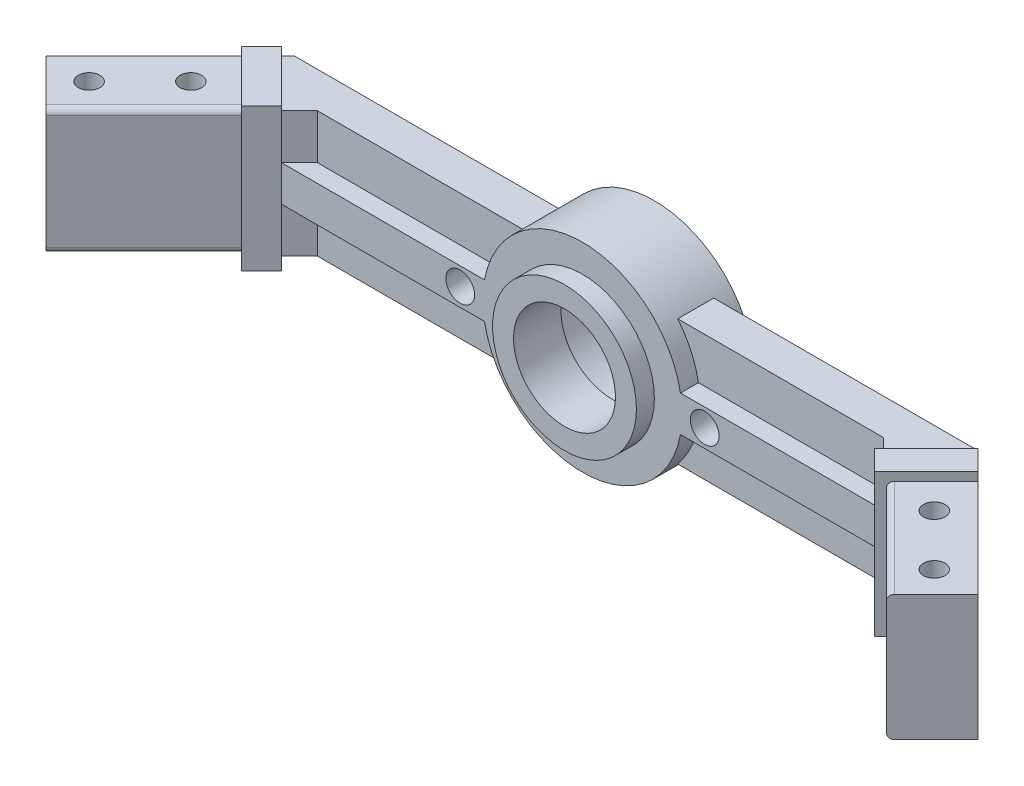
SolidWorks part; units mm, degrees
ref_plane "Front Plane" through (0, 0, 0) normal (0, 0, 1) x (1, 0, 0)
ref_plane "Top Plane" through (0, 0, 0) normal (0, 1, 0) x (1, 0, 0)
ref_plane "Right Plane" through (0, 0, 0) normal (1, 0, 0) x (0, 0, -1)
sketch "Sketch2" plane through (0, 0, 0) normal (0, 1, 0) x (1, 0, 0)
  line L0 (-57.15, 0) -> (57.15, 0)
  line L1 (57.15, 0) -> (84.0908, -26.9408)
  line L2 (0, 0) -> (0, 42.1572) construction
  line L3 (84.0908, -26.9408) -> (76.0085, -35.023)
  line L4 (76.0085, -35.023) -> (53.6855, -12.7)
  line L5 (53.6855, -12.7) -> (-53.6855, -12.7)
  line L6 (0, -12.7) -> (0, 0)
  line L7 (-76.0085, -35.023) -> (-53.6855, -12.7)
  line L8 (-84.0908, -26.9408) -> (-76.0085, -35.023)
  line L9 (-57.15, 0) -> (-84.0908, -26.9408)
  dimension "D1" = 135
  dimension "D2" = 57.15
  dimension "D3" = 38.1
  dimension "D4" = 12.7
  dimension "D5" = 11.43
extrude "Boss-Extrude1" add sketch "Sketch2" along normal mid plane 22.225 contours L0 L9 L8 L7 L5 L6 | L6 L5 L4 L3 L1 L0 region at (-42.209, 0, 10.6991) region at (42.209, 0, 10.6991)
sketch "Sketch3" plane through (0, 0, 0) normal (0, 0, -1) x (-1, 0, 0)
  circle A0 centre (0, 0) radius 11.25
  circle A1 centre (0, 0) radius 17.6
  circle A2 centre (0, 0) radius 9
  line M2 (-57.15, -11.1125) -> (57.15, -11.1125)
  line M4 (57.15, 11.1125) -> (-57.15, 11.1125)
  dimension "D1" = 22.5
  dimension "D2" = 6.35
  dimension "D3" = 18
extrude "Boss-Extrude2" add sketch "Sketch3" against normal up to surface (12.7 mm away) contours A1 up to face at (0, 0, 12.7)
extrude "Cut-Extrude2" cut sketch "Sketch3<5>" against normal blind 7.5 contours A0 M4 M2 | A2 | A0 M4 | A0 region at (-8.312, -7.1033, 0) region at (0, 11.1675, 0) region at (0, 0, 0)
sketch "Sketch3<5>" plane through (0, 0, 0) normal (0, 0, -1) x (-1, 0, 0) same geometry as "Sketch3"
extrude "Cut-Extrude3" cut sketch "Sketch3<6>" against normal up to surface (12.7 mm away) contours A2 up to face at (0, 0, 12.7)
sketch "Sketch3<6>" plane through (0, 0, 0) normal (0, 0, -1) x (-1, 0, 0) same geometry as "Sketch3"
sketch "Sketch4" plane through (55.5158, 0, 55.5158) normal (0.7071, 0, 0.7071) x (0.7071, 0, -0.7071)
  line L0 (34.6962, 11.1125) -> (34.6962, -11.1125) construction
  line L2 (40.4112, -12.6125) -> (27.4812, -12.6125)
  line L3 (40.4112, -12.6125) -> (40.4112, 12.6125)
  line L4 (28.9812, -11.1125) -> (40.4112, -11.1125)
  line L5 (40.4112, -11.1125) -> (40.4112, 11.1125)
  line L6 (40.4112, 11.1125) -> (28.9812, 11.1125)
  line L7 (28.9812, 11.1125) -> (28.9812, -11.1125)
  line L8 (28.9812, -11.1125) -> (40.4112, -11.1125)
  line L9 (40.4112, -11.1125) -> (40.4112, 11.1125)
  line L10 (40.4112, 11.1125) -> (28.9812, 11.1125)
  line L11 (28.9812, 11.1125) -> (28.9812, -11.1125)
  line L12 (40.4112, 12.6125) -> (27.4812, 12.6125)
  line L13 (27.4812, -12.6125) -> (27.4812, 12.6125)
  line M9 (28.9812, -11.1125) -> (40.4112, -11.1125)
  line M11 (40.4112, 11.1125) -> (28.9812, 11.1125)
  line M12 (28.9812, 11.1125) -> (28.9812, -11.1125)
  dimension "D2" = 1.5
  dimension "D3" = 1.5
  dimension "D4" = 1.5
  dimension "D1" = 0
extrude "Boss-Extrude3" add sketch "Sketch4" against normal blind 3.175 and the other way blind 1.778 from offset 28.7528 contours L13 L2 L3 L8 L10 L12 M9 M12 M11 region at (79.5193, -12.329, 31.5122) offset against normal yes
fillet "Fillet1" radius 1.016 2 edges at (66.4715, -11.1125, 25.486) (66.4715, 11.1125, 25.486)
sketch "Sketch5" plane through (0, 11.1125, 0) normal (0, 1, 0) x (1, 0, 0)
  line L0 (80.2293, -30.8023) -> (61.1552, -11.7282) construction
  line L4 (65.0167, -7.8667) -> (57.6529, -15.2305)
  line L5 (57.6529, -15.2305) -> (76.727, -34.3046)
  line L6 (76.727, -34.3046) -> (84.0908, -26.9408)
  line L7 (84.0908, -26.9408) -> (65.0167, -7.8667)
  line L8 (65.0167, -7.8667) -> (57.6529, -15.2305)
  line L9 (57.6529, -15.2305) -> (76.727, -34.3046)
  line L10 (76.727, -34.3046) -> (84.0908, -26.9408)
  line L11 (84.0908, -26.9408) -> (65.0167, -7.8667)
  circle A0 centre (74.6256, -25.1986) radius 1.905
  circle A1 centre (65.6453, -16.2183) radius 1.905
  dimension "D4" = 3.81
  dimension "D2" = 6.35
  dimension "D3" = 12.7
  dimension "D5" = 5.461
  dimension "D1" = 0
extrude "Cut-Extrude4" cut sketch "Sketch5" against normal through all contours A0 L0 | L0 A0 | A1 region at (74.0539, 11.1125, 25.7703) region at (75.1973, 11.1125, 24.6269)
mirror "Mirror2" about plane through (0, 0, 0) normal (1, 0, 0) of "Boss-Extrude3", "Cut-Extrude4"
fillet "Fillet3" radius 1.016 2 edges at (-66.4715, -11.1125, 25.486) (-66.4715, 11.1125, 25.486)
sketch "Sketch6" plane through (0, 0, 12.7) normal (0, 0, 1) x (1, 0, 0)
  line L0 (-53.1788, 0) -> (53.1788, 0) construction
  line L1 (-53.1788, 3.175) -> (-17.3112, 3.175)
  line L2 (-53.1788, -3.175) -> (-17.3112, -3.175)
  line L3 (0, 0) -> (0, 17.6) construction
  line L4 (53.1788, -3.175) -> (17.3112, -3.175)
  line L5 (53.1788, 3.175) -> (17.3112, 3.175)
  line L6 (13.6482, -11.1125) -> (53.1788, -11.1125)
  line L7 (53.1788, -11.1125) -> (53.1788, 11.1125)
  line L8 (53.1788, 11.1125) -> (13.6482, 11.1125)
  line L9 (-13.6482, 11.1125) -> (-53.1788, 11.1125)
  line L11 (-53.1788, -11.1125) -> (-13.6482, -11.1125)
  line L12 (13.6482, -11.1125) -> (53.1788, -11.1125)
  line L14 (53.1788, 11.1125) -> (13.6482, 11.1125)
  line L15 (-13.6482, 11.1125) -> (-53.1788, 11.1125)
  line L17 (-53.1788, -11.1125) -> (-13.6482, -11.1125)
  line L29 (53.1788, -11.1125) -> (53.1788, 11.1125)
  line L31 (-53.1788, 11.1125) -> (-53.1788, -11.1125)
  line L34 (-53.1788, 11.1125) -> (-53.1788, -11.1125)
  circle A0 centre (0, 0) radius 9 construction
  circle A1 centre (0, 0) radius 9
  arc A2 (13.6482, 11.1125) -> (-13.6482, 11.1125) centre (0, 0) ccw
  arc A3 (-13.6482, -11.1125) -> (13.6482, -11.1125) centre (0, 0) ccw
  arc A4 (13.6482, 11.1125) -> (-13.6482, 11.1125) centre (0, 0) ccw
  arc A5 (-13.6482, -11.1125) -> (13.6482, -11.1125) centre (0, 0) ccw
  circle A6 centre (0, 0) radius 17.6
  line M16 (13.6482, -11.1125) -> (53.1788, -11.1125)
  line M17 (53.1788, -11.1125) -> (53.1788, 11.1125)
  line M18 (53.1788, 11.1125) -> (13.6482, 11.1125)
  line M20 (-13.6482, 11.1125) -> (-53.1788, 11.1125)
  line M22 (-53.1788, -11.1125) -> (-13.6482, -11.1125)
  dimension "D2" = 3.175
  dimension "D1" = 0
extrude "Cut-Extrude5" cut sketch "Sketch6" against normal blind 3.175 contours A6 L1 M20 | A6 L2 M22 | A6 L4 M16 M17 | A6 L5 M17 M18 region at (-34.5174, 7.2077, 12.7) region at (-34.5174, -7.2077, 12.7) region at (34.5174, 7.2077, 12.7) region at (34.5174, -7.2077, 12.7)
sketch "Sketch9" plane through (0, 0, 0) normal (0, 0, -1) x (-1, 0, 0)
  line L0 (0, 0) -> (-57.15, 0) construction
  line L1 (-57.15, 11.1125) -> (-57.15, -11.1125) construction
  line L2 (-17.3112, -3.175) -> (-68.1112, -3.175)
  line L3 (-68.1112, -3.175) -> (-68.1112, 3.175)
  line L4 (-17.3112, 3.175) -> (-68.1112, 3.175)
  line L5 (0, 19.2626) -> (0, -19.2626) construction
  line L6 (68.1112, -3.175) -> (68.1112, 3.175)
  line L7 (17.3112, 3.175) -> (68.1112, 3.175)
  line L8 (17.3112, -3.175) -> (68.1112, -3.175)
  line L10 (-57.15, -11.1125) -> (-68.1112, -11.1125)
  line L11 (-57.15, -11.1125) -> (-57.15, -3.175)
  line L12 (-57.15, -3.175) -> (-68.1112, -3.175)
  line L13 (-68.1112, -11.1125) -> (-68.1112, -3.175)
  line L14 (-68.1112, 3.175) -> (-57.15, 3.175)
  line L15 (57.15, 11.1125) -> (13.6482, 11.1125)
  line L16 (-13.6482, 11.1125) -> (-57.15, 11.1125)
  line L17 (-57.15, 11.1125) -> (-57.15, -11.1125)
  line L18 (-57.15, -11.1125) -> (-13.6482, -11.1125)
  line L19 (13.6482, -11.1125) -> (57.15, -11.1125)
  line L20 (57.15, -11.1125) -> (57.15, 11.1125)
  line L21 (57.15, 11.1125) -> (13.6482, 11.1125)
  line L22 (-13.6482, 11.1125) -> (-57.15, 11.1125)
  line L23 (-57.15, 11.1125) -> (-57.15, -11.1125)
  line L24 (-57.15, -11.1125) -> (-13.6482, -11.1125)
  line L25 (13.6482, -11.1125) -> (57.15, -11.1125)
  line L26 (57.15, -11.1125) -> (57.15, 11.1125)
  line L27 (-68.1112, 3.175) -> (-68.1112, 11.1125)
  line L28 (-68.1112, 11.1125) -> (-57.15, 11.1125)
  line L29 (-57.15, 3.175) -> (-57.15, 11.1125)
  line L30 (68.1112, -3.175) -> (57.15, -3.175)
  line L31 (68.1112, -3.175) -> (68.1112, -11.1125)
  line L32 (68.1112, -11.1125) -> (57.15, -11.1125)
  line L33 (57.15, -3.175) -> (57.15, -11.1125)
  line L34 (68.1112, 3.175) -> (57.15, 3.175)
  line L35 (68.1112, 3.175) -> (68.1112, 11.1125)
  line L36 (68.1112, 11.1125) -> (57.15, 11.1125)
  line L37 (57.15, 3.175) -> (57.15, 11.1125)
  circle A0 centre (0, 0) radius 17.6
  arc A3 (13.6482, 11.1125) -> (-13.6482, 11.1125) centre (0, 0) ccw
  arc A4 (-13.6482, -11.1125) -> (13.6482, -11.1125) centre (0, 0) ccw
  arc A5 (13.6482, 11.1125) -> (-13.6482, 11.1125) centre (0, 0) ccw
  arc A6 (-13.6482, -11.1125) -> (13.6482, -11.1125) centre (0, 0) ccw
  point P11 (-68.1112, 0)
  line M3 (57.15, 11.1125) -> (13.6482, 11.1125)
  line M5 (-13.6482, 11.1125) -> (-57.15, 11.1125)
  line M6 (-57.15, 11.1125) -> (-57.15, -11.1125)
  line M7 (-57.15, -11.1125) -> (-13.6482, -11.1125)
  line M9 (13.6482, -11.1125) -> (57.15, -11.1125)
  line M10 (57.15, -11.1125) -> (57.15, 11.1125)
  dimension "D1" = 3.175
  dimension "D2" = 50.8
  dimension "D3" = 0
extrude "Cut-Extrude6" cut sketch "Sketch9" against normal blind 3.175 contours L32 L31 L8 M10 | A0 L8 M9 M10 | A0 L7 M10 M3 | L35 L36 L7 M10 | A0 L2 M6 M7 | L13 L10 L2 M6 | A0 L4 M5 M6 | L28 L27 L4 M6 region at (36.5044, -7.2016, 0) region at (62.6306, -7.1438, 0) region at (36.5044, 7.2016, 0) region at (62.6306, 7.1437, 0) region at (-36.5044, -7.2016, 0) region at (-36.5044, 7.2016, 0) region at (-62.6306, -7.1438, 0) region at (-62.6306, 7.1437, 0)
sketch "Sketch12" plane through (55.5158, 0, 55.5158) normal (0.7071, 0, 0.7071) x (0.7071, 0, -0.7071)
  line L4 (28.9812, 10.0965) -> (28.9812, -10.0965)
  line L5 (29.9972, -11.1125) -> (40.4112, -11.1125)
  line L6 (40.4112, -11.1125) -> (40.4112, 11.1125)
  line L7 (40.4112, 11.1125) -> (29.9972, 11.1125)
  line L8 (28.9812, 10.0965) -> (28.9812, -10.0965)
  line L9 (29.9972, -11.1125) -> (40.4112, -11.1125)
  line L10 (40.4112, -11.1125) -> (40.4112, 11.1125)
  line L11 (40.4112, 11.1125) -> (29.9972, 11.1125)
  arc A2 (28.9812, -10.0965) -> (29.9972, -11.1125) centre (29.9972, -10.0965) ccw
  arc A3 (29.9972, 11.1125) -> (28.9812, 10.0965) centre (29.9972, 10.0965) ccw
  arc A4 (28.9812, -10.0965) -> (29.9972, -11.1125) centre (29.9972, -10.0965) ccw
  arc A5 (29.9972, 11.1125) -> (28.9812, 10.0965) centre (29.9972, 10.0965) ccw
  dimension "D1" = 0
extrude "Cut-Extrude9" cut sketch "Sketch12" against normal blind 2.54
mirror "Mirror3" about plane through (0, 0, 0) normal (1, 0, 0) of "Cut-Extrude9"
sketch "Sketch13" plane through (0, 0, 12.7) normal (0, 0, 1) x (1, 0, 0)
  circle A0 centre (0, 0) radius 9 construction
  circle A1 centre (0, 0) radius 9
  circle A2 centre (0, 0) radius 12.7
  dimension "D1" = 25.4
extrude "Boss-Extrude6" add sketch "Sketch13" along normal blind 3.175
chamfer "Chamfer2" distance 3.175 angle 45 4 edges at (53.1788, 7.1437, 9.525) (53.1788, -7.1437, 9.525) (-53.1788, 7.1437, 9.525) (-53.1788, -7.1437, 9.525)
sketch "Sketch14" plane through (0, 0, 0) normal (0, 0, -1) x (-1, 0, 0)
  line L6 (57.15, 3.175) -> (17.3112, 3.175)
  line L7 (-17.3112, 3.175) -> (-57.15, 3.175)
  line L8 (-57.15, 3.175) -> (-57.15, -3.175)
  line L9 (-57.15, -3.175) -> (-17.3112, -3.175)
  line L10 (17.3112, -3.175) -> (57.15, -3.175)
  line L11 (57.15, -3.175) -> (57.15, 3.175)
  line L12 (57.15, 3.175) -> (17.3112, 3.175)
  line L13 (-17.3112, 3.175) -> (-57.15, 3.175)
  line L14 (-57.15, 3.175) -> (-57.15, -3.175)
  line L15 (-57.15, -3.175) -> (-17.3112, -3.175)
  line L16 (17.3112, -3.175) -> (57.15, -3.175)
  line L17 (57.15, -3.175) -> (57.15, 3.175)
  circle A0 centre (0, 0) radius 11.25 construction
  circle A1 centre (0, 0) radius 11.25
  arc A2 (17.3112, 3.175) -> (-17.3112, 3.175) centre (0, 0) ccw
  arc A3 (-17.3112, -3.175) -> (17.3112, -3.175) centre (0, 0) ccw
  arc A4 (17.3112, 3.175) -> (-17.3112, 3.175) centre (0, 0) ccw
  arc A5 (-17.3112, -3.175) -> (17.3112, -3.175) centre (0, 0) ccw
  dimension "D1" = 0
sketch "Sketch15" plane through (0, 0, 0) normal (0, 0, -1) x (-1, 0, 0)
  line L0 (0, 0) -> (0, -17.6) construction
  arc A0 (-17.3112, -3.175) -> (17.3112, -3.175) centre (0, 0) ccw construction
  circle A1 centre (21.59, 0) radius 2.54
  circle A2 centre (-21.59, 0) radius 2.54
  dimension "D1" = 5.08
  dimension "D2" = 21.59
extrude "Cut-Extrude10" cut sketch "Sketch15" against normal through all contours A1 | A2
sketch "Sketch16" plane through (0, -11.1125, 0) normal (0, -1, 0) x (1, 0, 0)
  line L0 (74.9309, 32.5085) -> (74.2125, 33.2269) construction
  line L1 (74.2125, 33.2269) -> (56.9345, 15.9489) construction
  line L2 (57.6529, 15.2305) -> (56.9345, 15.9489) construction
  line L3 (-56.9345, 15.9489) -> (-74.2125, 33.2269) construction
  line L4 (-74.2125, 33.2269) -> (-74.9309, 32.5085) construction
  line L5 (-56.9345, 15.9489) -> (-57.6529, 15.2305) construction
  line L6 (-65.0167, 7.8667) -> (-61.5144, 4.3644) construction
  line L7 (-61.5144, 4.3644) -> (-52.3715, 13.5073) construction
  line L8 (-52.3715, 13.5073) -> (-55.8738, 17.0096) construction
  line L9 (-55.8738, 17.0096) -> (-65.0167, 7.8667) construction
  line L10 (55.8738, 17.0096) -> (52.3715, 13.5073) construction
  line L11 (52.3715, 13.5073) -> (61.5144, 4.3644) construction
  line L12 (61.5144, 4.3644) -> (65.0167, 7.8667) construction
  line L13 (65.0167, 7.8667) -> (55.8738, 17.0096) construction
  line L14 (17.3112, 9.525) -> (13.6482, 9.525) construction
  line L15 (17.3112, 12.7) -> (-17.3112, 12.7) construction
  line L16 (-13.6482, 9.525) -> (-17.3112, 9.525) construction
  line L17 (-17.3112, 3.175) -> (-13.6482, 3.175) construction
  line L18 (-17.3112, 0) -> (17.3112, 0) construction
  line L19 (13.6482, 3.175) -> (17.3112, 3.175) construction
  line L20 (-17.3112, 12.7) -> (-53.1788, 12.7) construction
  line L21 (-53.1788, 12.7) -> (-50.0038, 9.525) construction
  line L22 (-50.0038, 9.525) -> (-17.3112, 9.525) construction
  line L23 (-60.325, 3.175) -> (-57.15, 0) construction
  line L24 (-57.15, 0) -> (-17.3112, 0) construction
  line L25 (-17.3112, 3.175) -> (-60.325, 3.175) construction
  line L26 (17.3112, 9.525) -> (50.0038, 9.525) construction
  line L27 (50.0038, 9.525) -> (53.1788, 12.7) construction
  line L28 (53.1788, 12.7) -> (17.3112, 12.7) construction
  line L29 (57.15, 0) -> (60.325, 3.175) construction
  line L30 (60.325, 3.175) -> (17.3112, 3.175) construction
  line L31 (17.3112, 0) -> (57.15, 0) construction
  line L32 (-74.9309, 32.5085) -> (-82.2947, 25.1447) construction
  line L33 (-82.2947, 25.1447) -> (-65.0167, 7.8667) construction
  line L34 (-65.0167, 7.8667) -> (-57.6529, 15.2305) construction
  line L35 (-60.325, 3.175) -> (-13.6482, 3.175) construction
  line L36 (-13.6482, 9.525) -> (-50.0038, 9.525) construction
  line L37 (-50.0038, 9.525) -> (-53.1788, 12.7) construction
  line L38 (-53.1788, 12.7) -> (-61.5144, 4.3644) construction
  line L39 (-61.5144, 4.3644) -> (-60.325, 3.175) construction
  line L40 (13.6482, 3.175) -> (60.325, 3.175) construction
  line L41 (60.325, 3.175) -> (61.5144, 4.3644) construction
  line L42 (61.5144, 4.3644) -> (53.1788, 12.7) construction
  line L43 (53.1788, 12.7) -> (50.0038, 9.525) construction
  line L44 (50.0038, 9.525) -> (13.6482, 9.525) construction
  line L45 (82.2947, 25.1447) -> (74.9309, 32.5085) construction
  line L46 (57.6529, 15.2305) -> (65.0167, 7.8667) construction
  line L47 (65.0167, 7.8667) -> (82.2947, 25.1447) construction
  line L48 (74.9309, 32.5085) -> (74.2125, 33.2269)
  line L49 (74.2125, 33.2269) -> (56.9345, 15.9489)
  line L50 (57.6529, 15.2305) -> (56.9345, 15.9489)
  line L51 (-56.9345, 15.9489) -> (-74.2125, 33.2269)
  line L52 (-74.2125, 33.2269) -> (-74.9309, 32.5085)
  line L53 (-56.9345, 15.9489) -> (-57.6529, 15.2305)
  line L54 (-65.0167, 7.8667) -> (-61.5144, 4.3644)
  line L55 (-61.5144, 4.3644) -> (-52.3715, 13.5073)
  line L56 (-52.3715, 13.5073) -> (-55.8738, 17.0096)
  line L57 (-55.8738, 17.0096) -> (-65.0167, 7.8667)
  line L58 (55.8738, 17.0096) -> (52.3715, 13.5073)
  line L59 (52.3715, 13.5073) -> (61.5144, 4.3644)
  line L60 (61.5144, 4.3644) -> (65.0167, 7.8667)
  line L61 (65.0167, 7.8667) -> (55.8738, 17.0096)
  line L62 (17.3112, 9.525) -> (13.6482, 9.525)
  line L63 (17.3112, 12.7) -> (-17.3112, 12.7)
  line L64 (-13.6482, 9.525) -> (-17.3112, 9.525)
  line L65 (-17.3112, 3.175) -> (-13.6482, 3.175)
  line L66 (-17.3112, 0) -> (17.3112, 0)
  line L67 (13.6482, 3.175) -> (17.3112, 3.175)
  line L68 (-17.3112, 12.7) -> (-53.1788, 12.7)
  line L69 (-53.1788, 12.7) -> (-50.0038, 9.525)
  line L70 (-50.0038, 9.525) -> (-17.3112, 9.525)
  line L71 (-60.325, 3.175) -> (-57.15, 0)
  line L72 (-57.15, 0) -> (-17.3112, 0)
  line L73 (-17.3112, 3.175) -> (-60.325, 3.175)
  line L74 (17.3112, 9.525) -> (50.0038, 9.525)
  line L75 (50.0038, 9.525) -> (53.1788, 12.7)
  line L76 (53.1788, 12.7) -> (17.3112, 12.7)
  line L77 (57.15, 0) -> (60.325, 3.175)
  line L78 (60.325, 3.175) -> (17.3112, 3.175)
  line L79 (17.3112, 0) -> (57.15, 0)
  line L80 (-74.9309, 32.5085) -> (-82.2947, 25.1447)
  line L81 (-82.2947, 25.1447) -> (-65.0167, 7.8667)
  line L82 (-65.0167, 7.8667) -> (-57.6529, 15.2305)
  line L83 (-60.325, 3.175) -> (-13.6482, 3.175)
  line L84 (-13.6482, 9.525) -> (-50.0038, 9.525)
  line L85 (-50.0038, 9.525) -> (-53.1788, 12.7)
  line L86 (-53.1788, 12.7) -> (-61.5144, 4.3644)
  line L87 (-61.5144, 4.3644) -> (-60.325, 3.175)
  line L88 (13.6482, 3.175) -> (60.325, 3.175)
  line L89 (60.325, 3.175) -> (61.5144, 4.3644)
  line L90 (61.5144, 4.3644) -> (53.1788, 12.7)
  line L91 (53.1788, 12.7) -> (50.0038, 9.525)
  line L92 (50.0038, 9.525) -> (13.6482, 9.525)
  line L93 (82.2947, 25.1447) -> (74.9309, 32.5085)
  line L94 (57.6529, 15.2305) -> (65.0167, 7.8667)
  line L95 (65.0167, 7.8667) -> (82.2947, 25.1447)
